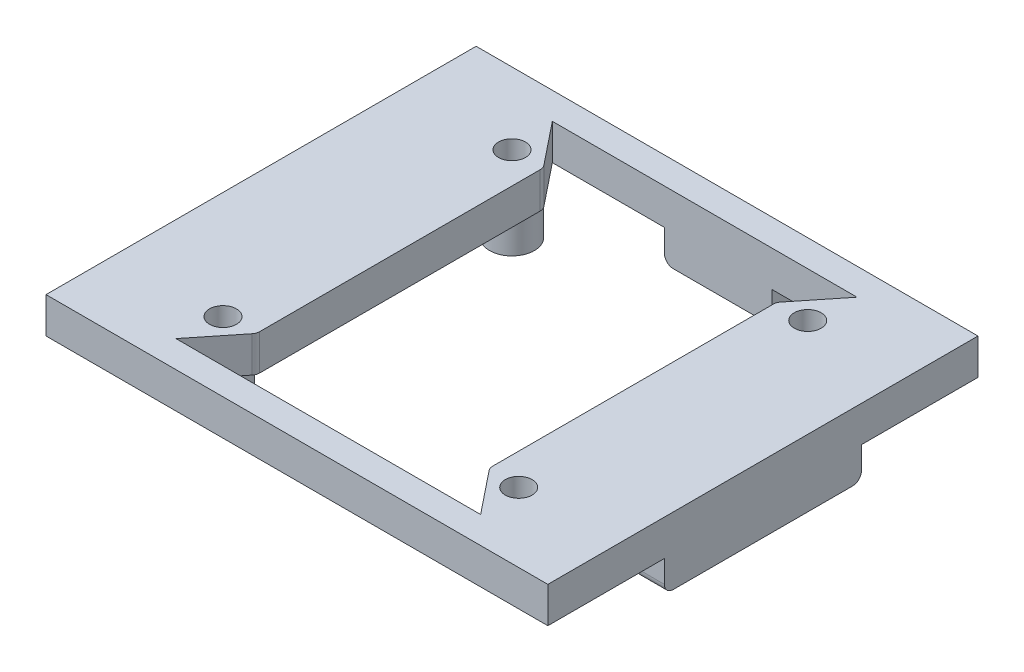
SolidWorks part; units mm, degrees
ref_plane "Front Plane" through (0, 0, 0) normal (0, 0, 1) x (1, 0, 0)
ref_plane "Top Plane" through (0, 0, 0) normal (0, 1, 0) x (1, 0, 0)
ref_plane "Right Plane" through (0, 0, 0) normal (1, 0, 0) x (0, 0, -1)
sketch "Sketch1" plane through (0, 0, 0) normal (0, 1, 0) x (1, 0, 0)
  circle A0 centre (-21.1373, 20.1176) radius 1.5
  circle A1 centre (11.8627, 20.1176) radius 1.5
  circle A2 centre (11.8627, -12.1324) radius 1.5
  circle A3 centre (-21.1373, -12.1324) radius 1.5
  circle A5 centre (-21.1373, 20.1176) radius 2.5
  circle A6 centre (11.8627, 20.1176) radius 2.5
  circle A7 centre (-21.1373, -12.1324) radius 2.5
  circle A8 centre (11.8627, -12.1324) radius 2.5
  dimension "D1" = 33
  dimension "D3" = 33
  dimension "D2" = 32.25
extrude "Boss-Extrude1" add sketch "Sketch1" along normal blind 6 and the other way blind 2.5
sketch "Sketch2" plane through (0, 6, 0) normal (0, 1, 0) x (1, 0, 0)
  line L1 (-30.1373, 25.1176) -> (19.8627, 25.1176)
  line L2 (-30.1373, 25.1176) -> (-30.1373, -16.8824)
  line L3 (-30.1373, -16.8824) -> (19.8627, -16.8824)
  line L4 (19.8627, 25.1176) -> (19.8627, -16.8824)
  circle A0 centre (-21.1373, 20.1176) radius 1.5 construction
  circle A1 centre (11.8627, 20.1176) radius 1.5 construction
  circle A2 centre (-21.1373, -12.1324) radius 1.5 construction
  circle A3 centre (11.8627, -12.1324) radius 1.5 construction
  dimension "D4" = 8
  dimension "D5" = 4.75
  dimension "D6" = 5
  dimension "D7" = 5
  dimension "D8" = 8
  dimension "D9" = 4.75
  dimension "D10" = 9
  dimension "D1" = 50
  dimension "D2" = 42
  dimension "D3" = 9
extrude "Boss-Extrude3" add sketch "Sketch2" against normal blind 4
sketch "Sketch3" plane through (0, 6, 0) normal (0, 1, 0) x (1, 0, 0)
  line L0 (-30.1373, 25.1176) -> (-30.1373, -16.8824) construction
  line L1 (-30.1373, -16.8824) -> (19.8627, -16.8824) construction
  line L4 (19.8627, 25.1176) -> (-30.1373, 25.1176) construction
  line L5 (19.8627, -16.8824) -> (19.8627, 25.1176) construction
  circle A0 centre (-21.1373, 20.1176) radius 1.5
  circle A2 centre (-21.1373, -12.1324) radius 1.5
  circle A3 centre (11.8627, -12.1324) radius 1.5
  circle A4 centre (11.8627, 20.1176) radius 1.5
  dimension "D1" = 8
  dimension "D4" = 5
  dimension "D5" = 9
  dimension "D6" = 4.75
  dimension "D7" = 5
  dimension "D9" = 4.75
  dimension "D10" = 8
  dimension "D11" = 9
sketch "Sketch4" plane through (0, 6, 0) normal (0, 1, 0) x (1, 0, 0)
  line L1 (-17.6373, 20.1176) -> (8.3627, 20.1176)
  line L2 (-17.6373, 20.1176) -> (-17.6373, -11.8824)
  line L3 (-17.6373, -11.8824) -> (8.3627, -11.8824)
  line L4 (8.3627, 20.1176) -> (8.3627, -11.8824)
  line L5 (-30.1373, 25.1176) -> (-30.1373, -16.8824) construction
  line L6 (19.8627, -16.8824) -> (19.8627, 25.1176) construction
  line L7 (-30.1373, -16.8824) -> (19.8627, -16.8824) construction
  line L8 (19.8627, 25.1176) -> (-30.1373, 25.1176) construction
  dimension "D1" = 26
  dimension "D2" = 32
  dimension "D3" = 12.5
  dimension "D4" = 11.5
  dimension "D5" = 5
  dimension "D6" = 5
extrude "Cut-Extrude2" cut sketch "Sketch4" against normal through all both and the other way through all
sketch "Sketch5" plane through (0, 2, 0) normal (0, -1, 0) x (1, 0, 0)
  line L0 (19.8627, -25.1176) -> (-30.1373, -25.1176) construction
  line L1 (19.8627, 6.8824) -> (22.8627, 6.8824)
  line L2 (19.8627, 6.8824) -> (19.8627, -15.1176)
  line L3 (19.8627, -15.1176) -> (22.8627, -15.1176)
  line L4 (22.8627, 6.8824) -> (22.8627, -15.1176)
  line L6 (19.8627, 16.8824) -> (19.8627, -25.1176) construction
  dimension "D1" = 22
  dimension "D2" = 10
  dimension "D3" = 3
  dimension "D4" = 3
extrude "Boss-Extrude4" add sketch "Sketch5" along normal blind 3.5 and the other way blind 4
sketch "Sketch6" plane through (0, 2, 0) normal (0, -1, 0) x (1, 0, 0)
  line L0 (19.8627, -15.1176) -> (19.8627, -25.1176) construction
  line L1 (-9.1373, -25.1176) -> (2.8627, -25.1176)
  line L2 (-9.1373, -25.1176) -> (-9.1373, -28.1176)
  line L3 (-9.1373, -28.1176) -> (2.8627, -28.1176)
  line L4 (2.8627, -25.1176) -> (2.8627, -28.1176)
  line L7 (19.8627, -25.1176) -> (-30.1373, -25.1176) construction
  dimension "D1" = 3
  dimension "D2" = 12
  dimension "D3" = 17
extrude "Boss-Extrude5" add sketch "Sketch6" along normal blind 3.5 and the other way blind 4
extrude "Cut-Extrude3" cut sketch "Sketch3" against normal blind 6
sketch "Sketch9" plane through (0, 6, 0) normal (0, 1, 0) x (1, 0, 0)
  line L1 (-30.1373, -16.8824) -> (19.8627, -16.8824)
  line L2 (-30.1373, -16.8824) -> (-30.1373, -19.8824)
  line L3 (-30.1373, -19.8824) -> (19.8627, -19.8824)
  line L4 (19.8627, -16.8824) -> (19.8627, -19.8824)
  line L5 (-30.1373, 25.1176) -> (-33.1373, 25.1176)
  line L6 (-30.1373, 25.1176) -> (-30.1373, -19.8824)
  line L7 (-30.1373, -19.8824) -> (-33.1373, -19.8824)
  line L8 (-33.1373, 25.1176) -> (-33.1373, -19.8824)
  line L13 (19.8627, 28.1176) -> (22.8627, 28.1176)
  line L14 (19.8627, 28.1176) -> (19.8627, 15.1176)
  line L15 (19.8627, 15.1176) -> (22.8627, 15.1176)
  line L16 (22.8627, 28.1176) -> (22.8627, 15.1176)
  line L17 (19.8627, -19.8824) -> (22.8627, -19.8824)
  line L18 (19.8627, -19.8824) -> (19.8627, -6.881)
  line L19 (19.8627, -6.881) -> (22.8627, -6.881)
  line L20 (22.8627, -19.8824) -> (22.8627, -6.881)
  line L21 (-9.1373, 28.1176) -> (-33.1373, 28.1176)
  line L22 (-9.1373, 28.1176) -> (-9.1373, 25.1176)
  line L23 (-9.1373, 25.1176) -> (-33.1373, 25.1176)
  line L24 (-33.1373, 28.1176) -> (-33.1373, 25.1176)
  line L25 (2.8627, 28.1176) -> (19.8627, 28.1176)
  line L26 (2.8627, 28.1176) -> (2.8627, 25.1176)
  line L27 (2.8627, 25.1176) -> (19.8627, 25.1176)
  line L28 (19.8627, 28.1176) -> (19.8627, 25.1176)
  line M22 (-30.1373, 25.1176) -> (-30.1373, -16.8824)
  line M23 (-30.1373, -16.8824) -> (19.8627, -16.8824)
  line M24 (19.8627, -16.8824) -> (19.8627, -6.8824)
  line M25 (19.8627, -6.8824) -> (22.8627, -6.8824)
  line M29 (19.8627, 25.1176) -> (2.8627, 25.1176)
  line M30 (2.8627, 25.1176) -> (2.8627, 28.1176)
  line M32 (-9.1373, 28.1176) -> (-9.1373, 25.1176)
  line M33 (-9.1373, 25.1176) -> (-30.1373, 25.1176)
  dimension "D2" = 3
  dimension "D3" = 3
  dimension "D4" = 3
  dimension "D5" = 3
  dimension "D6" = 13
  dimension "D7" = 13.0013
extrude "Boss-Extrude6" add sketch "Sketch9" against normal blind 4 separate body contours L5 M33 M32 | L5 L8 L7 L2 M22 | L4 L2 L3 M23 | L17 L20 L4 M25 M24 | L25 L14 M30 M29 | L14 L15 L16 L13 region at (-5.1373, 6, 18.3824) region at (-31.6373, 6, -2.6176) region at (21.3627, 6, 13.3824) region at (-21.1373, 6, -26.6176) region at (11.3627, 6, -26.6176)
sketch "Sketch10" plane through (0, 6, 0) normal (0, 1, 0) x (1, 0, 0)
  line L0 (8.3627, 20.1176) -> (12.3627, 25.1176)
  line L1 (19.8627, 25.1176) -> (2.8627, 25.1176) construction
  line L2 (12.3627, 25.1176) -> (-21.6373, 25.1176)
  line L3 (-9.1373, 25.1176) -> (-30.1373, 25.1176) construction
  line L4 (-21.6373, 25.1176) -> (-17.6373, 20.1176)
  line L5 (-17.6373, 20.1176) -> (8.3627, 20.1176)
  line L6 (-17.6373, -11.8824) -> (-21.6373, -16.8824)
  line L7 (-17.6373, -11.8824) -> (8.3627, -11.8824) construction
  line L8 (-30.1373, -16.8824) -> (19.8627, -16.8824) construction
  line L9 (-21.6373, -16.8824) -> (12.3627, -16.8824)
  line L10 (12.3627, -16.8824) -> (8.3627, -11.8824)
  line L11 (8.3627, -11.8824) -> (-17.6373, -11.8824)
  dimension "D1" = 4
  dimension "D2" = 4
  dimension "D3" = 4
  dimension "D4" = 4
extrude "Cut-Extrude6" cut sketch "Sketch10" against normal up to surface (4 mm away) up to face at (-4.6373, 2, -4.1176)
fillet "Fillet1" radius 1 2 edges at (-17.6373, 4, -20.1176) (-17.6373, 4, 11.8824)
fillet "Fillet2" radius 1 2 edges at (8.3627, 4, 11.8824) (8.3627, 4, -20.1176)
fillet "Fillet3" radius 1 2 edges at (-9.1373, -1.5, -26.6176) (2.8627, -1.5, -26.6176)
fillet "Fillet4" radius 1 2 edges at (21.3627, -1.5, -15.1176) (21.3627, -1.5, 6.8824)
combine bodies "Combine1" operation type add bodies to combine 114 120 116 121 113
